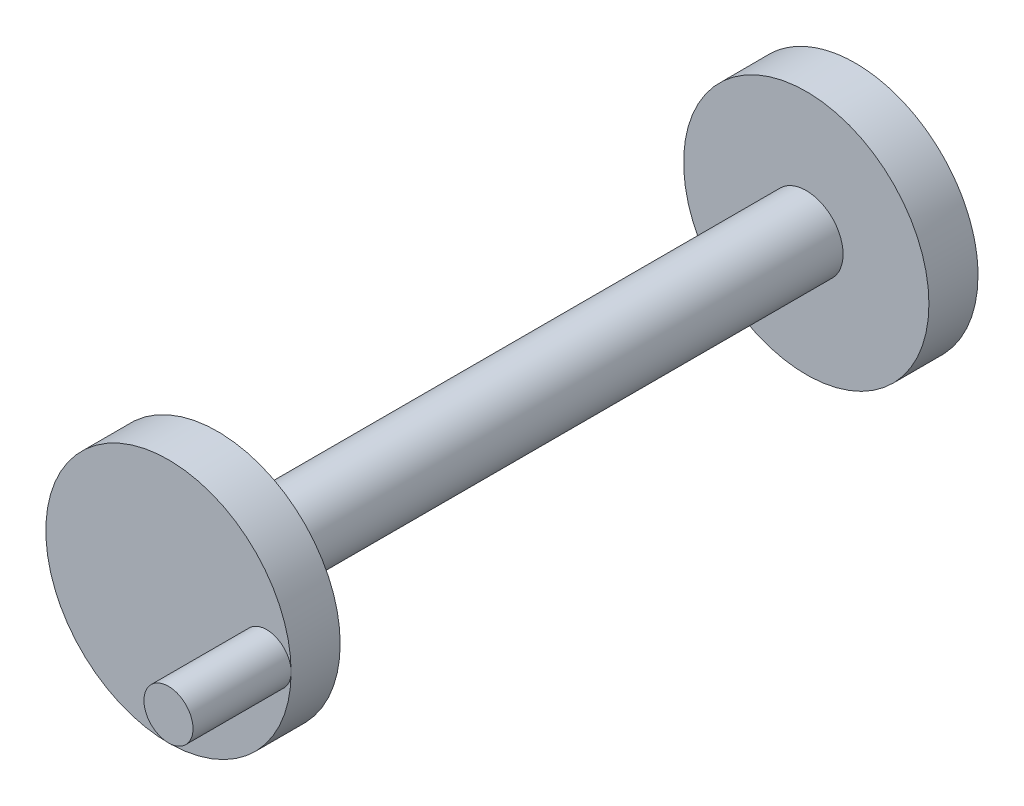
SolidWorks part; units mm, degrees
ref_plane "Front Plane" through (0, 0, 0) normal (0, 0, 1) x (1, 0, 0)
ref_plane "Top Plane" through (0, 0, 0) normal (0, 1, 0) x (1, 0, 0)
ref_plane "Right Plane" through (0, 0, 0) normal (1, 0, 0) x (0, 0, -1)
sketch "Sketch1" plane through (0, 0, 0) normal (0, 0, 1) x (1, 0, 0)
  line L0 (0, 1.7346) -> (0, -1.7346) construction
  circle A0 centre (0, 0) radius 2.5
  circle A1 centre (2, 0) radius 0.5
  circle A2 centre (0, 0) radius 0.75
  circle A3 centre (-2, 0) radius 0.5
  dimension "D1" = 5
  dimension "D2" = 1.5
  dimension "D4" = 1
  dimension "D3" = 2
extrude "Boss-Extrude1" add sketch "Sketch1" along normal blind 1 contours A0 A1 A2 | A1 | A2 | A3 | L0 A2 region at (0.3183, 0, 0) region at (-0.3183, 0, 0) region at (-2, 0, 0) region at (0, -2.4293, 0) region at (2, 0, 0)
extrude "Boss-Extrude2" add sketch "Sketch1<3>" against normal blind 12 contours A2 | A2 region at (0, 0, 0)
sketch "Sketch1<3>" plane through (0, 0, 0) normal (0, 0, 1) x (1, 0, 0) same geometry as "Sketch1"
extrude "Boss-Extrude4" add sketch "Sketch1<5>" along normal blind 2 from surface contours A1 region at (2, 0, 0) starting at face at (2.5, 0, 1)
sketch "Sketch1<5>" plane through (0, 0, 0) normal (0, 0, 1) x (1, 0, 0) same geometry as "Sketch1"
extrude "Boss-Extrude6" add sketch "Sketch1<7>" against normal blind 1 from surface contours A0 A3 A1 A2 | A1 | A3 | L0 A2 | A2 L0 region at (0.3183, 0, 0) region at (-0.3183, 0, 0) region at (-2, 0, 0) region at (0, -2.4293, 0) region at (2, 0, 0) starting at face at (0.75, 0, -12)
sketch "Sketch1<7>" plane through (0, 0, 0) normal (0, 0, 1) x (1, 0, 0) same geometry as "Sketch1"
extrude "Boss-Extrude7" add sketch "Sketch1<8>" against normal blind 2 from surface contours A3 region at (-2, 0, 0) starting at face at (2.5, 0, -13)
sketch "Sketch1<8>" plane through (0, 0, 0) normal (0, 0, 1) x (1, 0, 0) same geometry as "Sketch1"
